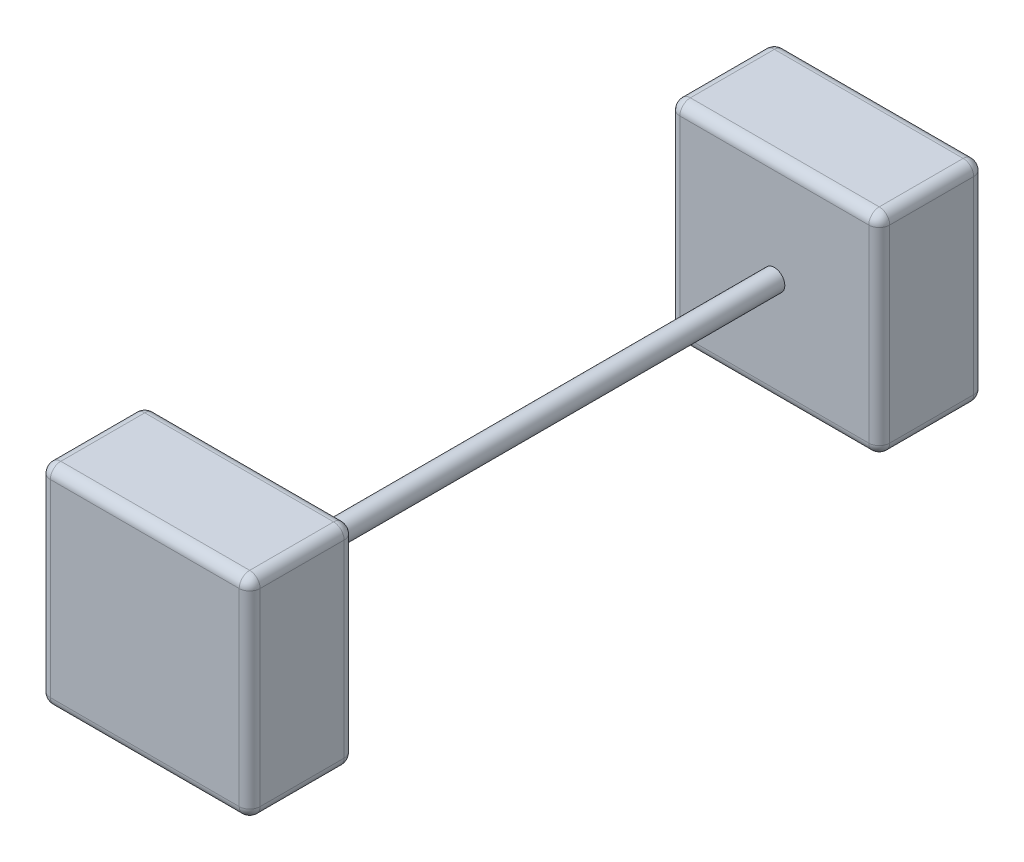
SolidWorks part; units mm, degrees
ref_plane "Front Plane" through (0, 0, 0) normal (0, 0, 1) x (1, 0, 0)
ref_plane "Top Plane" through (0, 0, 0) normal (0, 1, 0) x (1, 0, 0)
ref_plane "Right Plane" through (0, 0, 0) normal (1, 0, 0) x (0, 0, -1)
sketch "Sketch1" plane through (0, 0, 0) normal (0, 0, 1) x (1, 0, 0)
  line L1 (0, 0) -> (20, 0)
  line L2 (0, 0) -> (0, 20)
  line L3 (0, 20) -> (20, 20)
  line L4 (20, 0) -> (20, 20)
  dimension "D1" = 20
  dimension "D2" = 20
extrude "Boss-Extrude1" add sketch "Sketch1" along normal blind 10
sketch "Sketch3" plane through (0, 0, 0) normal (0, -1, 0) x (-1, 0, 0)
  line L0 (0, -10) -> (0, -60)
  line L1 (0, -60) -> (-20, -60)
  line L2 (-20, -60) -> (-20, -10)
  line L3 (-20, -10) -> (0, -10)
  line L9 (0, -60) -> (-20, -60)
  dimension "D1" = 20
  dimension "D2" = 50
sketch "Sketch4" plane through (0, 0, 0) normal (0, 1, 0) x (1, 0, 0)
  line L1 (0, -60) -> (20, -60)
  line L2 (0, -60) -> (0, -70)
  line L3 (0, -70) -> (20, -70)
  line L4 (20, -60) -> (20, -70)
  dimension "D1" = 10
  dimension "D2" = 20
extrude "Boss-Extrude2" add sketch "Sketch4" along normal blind 20 separate body
sketch "Sketch6" plane through (0, 0, 10) normal (0, 0, 1) x (1, 0, 0)
  circle A0 centre (10, 10) radius 1
  dimension "D1" = 2
fillet "Fillet6" radius 1 12 edges at (20, 10, 10) (10, 0, 10) (20, 0, 5) (20, 20, 5) (10, 20, 10) (0, 20, 5) (0, 10, 10) (0, 0, 5) (10, 0, 0) (20, 10, 0) (10, 20, 0) (0, 10, 0)
fillet "Fillet7" radius 1 12 edges at (0, 0, 65) (0, 10, 70) (10, 0, 70) (10, 20, 70) (0, 20, 65) (20, 10, 70) (20, 20, 65) (20, 0, 65) (20, 10, 60) (10, 20, 60) (0, 10, 60) (10, 0, 60)
extrude "Boss-Extrude3" add sketch "Sketch6" along normal up to next
